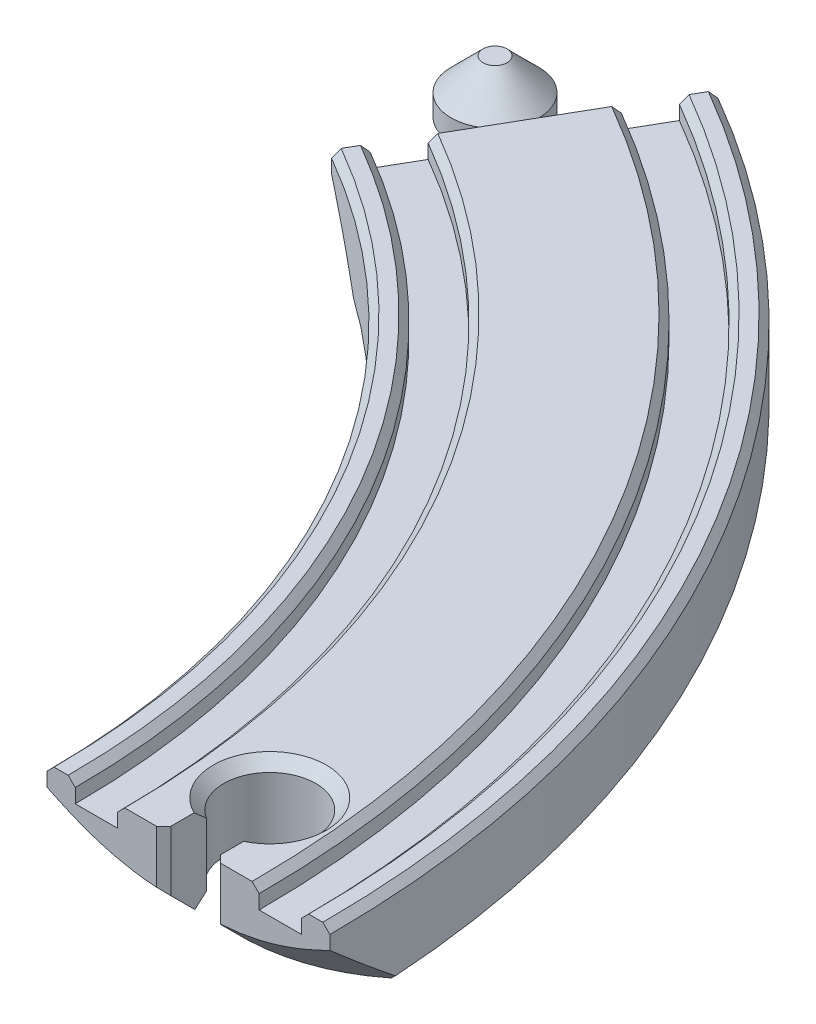
SolidWorks part; units mm, degrees
ref_plane "Front Plane" through (0, 0, 0) normal (0, 0, 1) x (1, 0, 0)
ref_plane "Top Plane" through (0, 0, 0) normal (0, 1, 0) x (1, 0, 0)
ref_plane "Right Plane" through (0, 0, 0) normal (1, 0, 0) x (0, 0, -1)
sketch "Sketch2" plane through (0, 0, 0) normal (0, 0, 1) x (1, 0, 0)
  line L0 (-20, 0) -> (20, 0)
  line L1 (20, 0) -> (20, 12)
  line L2 (20, 12) -> (16, 12)
  line L3 (16, 12) -> (16, 9)
  line L4 (16, 9) -> (10, 9)
  line L5 (10, 9) -> (10, 12)
  line L6 (10, 12) -> (-10, 12)
  line L7 (-10, 12) -> (-10, 9)
  line L8 (-10, 9) -> (-16, 9)
  line L9 (-16, 9) -> (-16, 12)
  line L10 (-16, 12) -> (-20, 12)
  line L11 (-20, 12) -> (-20, 0)
  line L12 (-129.9038, 0) -> (-129.9038, 12)
  point P4 (0, 0)
  dimension "D1" = 40
  dimension "D2" = 12
  dimension "D3" = 3
  dimension "D4" = 4
  dimension "D5" = 6
  dimension "D6" = 129.9038
revolve "Revolve1" add sketch "Sketch2" angle 60 about L12 region at (0, 5.6351, 0)
sketch "Sketch3" plane through (0, 12, 0) normal (0, 1, 0) x (1, 0, 0)
  line L0 (10, 0) -> (-10, 0) construction
  line L2 (-3.5, 0) -> (3.5, 0)
  line L3 (-3.5, 0) -> (-3.5, 11.5)
  line L4 (-3.5, 11.5) -> (3.5, 11.5)
  line L5 (3.5, 0) -> (3.5, 11.5)
  line L6 (-3.5, 0) -> (3.5, 11.5) construction
  line L7 (-3.5, 11.5) -> (3.5, 0) construction
  circle A0 centre (0, 11.5) radius 6.5
  point P4 (0, 5.75)
  point P10 (0, 0)
  line M6 (-10, 0) -> (10, 0)
  dimension "D1" = 13
  dimension "D2" = 11.5
  dimension "D3" = 7
extrude "Cut-Extrude1" cut sketch "Sketch3" against normal through all contours L5 A0 L3 L4 | L3 A0 L5 L4 | A0 L3 L5 M6 region at (0, 12, -2.6732) region at (0, 12, -12.9919) region at (0, 12, -8.4074)
sketch "Sketch4" plane through (0, 12, 0) normal (0, 1, 0) x (1, 0, 0)
  line L0 (-63.4519, 115.0981) -> (-66.4519, 109.9019)
  line L1 (-63.4519, 115.0981) -> (-73.4112, 120.8481)
  line L2 (-66.4519, 109.9019) -> (-76.4112, 115.6519)
  line L3 (-73.4112, 120.8481) -> (-76.4112, 115.6519)
  line L4 (-59.9519, 121.1603) -> (-69.9519, 103.8397) construction
  circle A0 centre (-74.9112, 118.25) radius 6.2
  point P9 (-64.9519, 112.5)
  line M6 (-59.9519, 121.1603) -> (-69.9519, 103.8397)
  dimension "D1" = 12.4
  dimension "D2" = 6
  dimension "D3" = 11.5
extrude "Boss-Extrude1" add sketch "Sketch4" against normal up to surface (12 mm away) contours L1 A0 L2 L3 | L2 A0 L1 L3 region at (-72.3315, 12, -116.7606) region at (-75.9935, 12, -118.8749) up to face at (-12.4699, 0, -33.3033)
extrude "Boss-Extrude2" add sketch "Sketch4<3>" against normal blind 7.5 contours A0 L2 L1 M6 region at (-67.3597, 12, -113.8902)
sketch "Sketch4<3>" plane through (0, 12, 0) normal (0, 1, 0) x (1, 0, 0) same geometry as "Sketch4"
extrude "Cut-Extrude2" cut sketch "Sketch4<5>" against normal blind 4.5 contours A0 L2 L1 M6 region at (-67.3597, 12, -113.8902)
sketch "Sketch4<5>" plane through (0, 12, 0) normal (0, 1, 0) x (1, 0, 0) same geometry as "Sketch4"
chamfer "Chamfer2" distance 4.5 angle 45 1 edges at (-81.1112, 12, -118.25)
chamfer "Chamfer5" distance 3 distance2 4.5 1 edges at (-74.9112, 0, -124.45) first distance on face at (-74.9112, 0, -124.45)
chamfer "Chamfer3" distance 1.5 angle 45 2 edges at (0, 0, -18) (0, 12, -18)
sketch "Sketch17" plane through (30.976, 0, -53.6519) normal (-0.5, 0, 0.866) x (0.866, 0, 0.5)
  line L0 (-118.5741, 10.5741) -> (-118.5741, 0)
  line L1 (-118.5741, 0) -> (-108, 0)
  line L2 (-108, 0) -> (-118.5741, 10.5741)
  line L4 (-83, -1.2652) -> (-83, 10.5741) construction
  dimension "D1" = 25
revolve "Cut-Revolve1" cut sketch "Sketch17" angle 90 about L4
ref_plane "Plane1" through (32.476, 0, -56.25) normal (-0.5, 0, 0.866) x (0.866, 0, 0.5)
mirror "Mirror1" about plane through (32.476, 0, -56.25) normal (-0.5, 0, 0.866) of "Cut-Revolve1"
chamfer "Chamfer4" distance 4.5 angle 45 1 edges at (-64.9519, 0, -112.5)
ref_plane "Plane2" through (-32.476, 0, -56.25) normal (-0.5, 0, -0.866) x (-0.866, 0, 0.5)
mirror "Mirror4" about plane through (-32.476, 0, -56.25) normal (-0.5, 0, -0.866) of "Cut-Revolve1", "Mirror1"
chamfer "Chamfer1" distance 1 angle 45 10 edges at (-0.0833, 12, -74.9519) (-3.5474, 12, -72.9519) (-8.7436, 12, -69.9519) (-26.0641, 12, -59.9519) (-31.2602, 12, -56.9519) (-34.7243, 12, -54.9519) (-0.0833, 0, -74.9519) (-34.7243, 0, -54.9519) (3.5, 8.2521, 0) (-3.5, 8.2521, 0)
